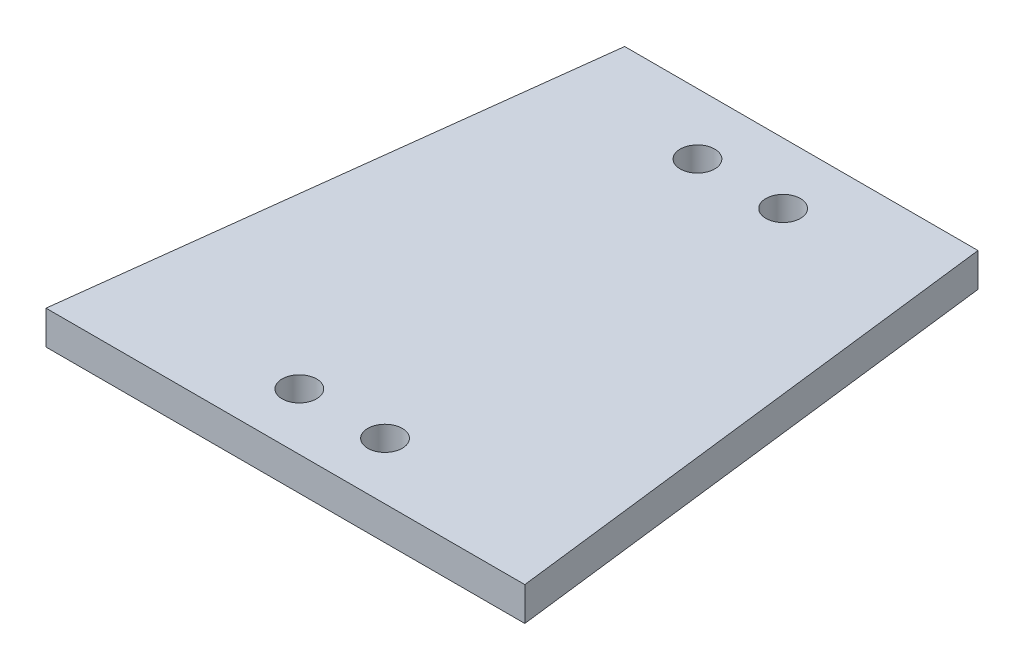
SolidWorks part; units mm, degrees
material "PET"
ref_plane "Front Plane" through (0, 0, 0) normal (0, 0, 1) x (1, 0, 0)
ref_plane "Top Plane" through (0, 0, 0) normal (0, 1, 0) x (1, 0, 0)
ref_plane "Right Plane" through (0, 0, 0) normal (1, 0, 0) x (0, 0, -1)
ref_plane "Plane1" through (0, -14, 0) normal (0, 1, 0) x (1, 0, 0)
sketch "Sketch1" plane through (0, -14, 0) normal (0, 1, 0) x (1, 0, 0)
  line L0 (-28.4185, 23.7577) -> (28.4185, 23.7577)
  line L1 (28.4185, 23.7577) -> (20.9705, 85)
  line L2 (20.9705, 85) -> (-20.9705, 85)
  line L3 (-20.9705, 85) -> (-28.4185, 23.7577)
extrude "Boss-Extrude1" add sketch "Sketch1" against normal blind 4
ref_plane "Plane2" through (0, 0, -64.665) normal (0, 0, -1) x (-1, 0, 0)
sketch "Sketch2" plane through (0, 0, -64.665) normal (0, 0, -1) x (-1, 0, 0)
  line L0 (-3, -29) -> (0, -29)
  line L1 (0, -29) -> (0, -18)
  line L2 (0, -18) -> (-5, -18)
  line L3 (-5, -18) -> (-5, -24)
  line L4 (-5, -24) -> (-3, -24)
  line L5 (-3, -24) -> (-3, -29)
  line L6 (0, -29) -> (0, -18) construction
revolve "Revolve1" add sketch "Sketch2" angle 360 about L6 reverse direction yes
hole_wizard "Ø4.1 (4.1) Diameter Hole1" positions "Sketch4" profile "Sketch3" hole size "Ø4.1" standard "ANSI Metric"
sketch "Sketch4" plane through (0, -14, 0) normal (0, 1, 0) x (1, 0, 0)
  point P0 (-5.085, 30.495)
  point P1 (5.085, 30.495)
  point P2 (5.085, 77.755)
  point P3 (-5.085, 77.755)
sketch "Sketch3" plane through (-5.085, -14, -30.495) normal (1, 0, 0) x (0, 0, 1)
  line L0 (0, 0) -> (0, 15)
  line L1 (0, 15) -> (2.05, 15)
  line L2 (2.05, 15) -> (2.05, 0)
  line L5 (2.05, 0) -> (0, 0)
  line L11 (0, -6.35) -> (0, 107.95) construction
  dimension "Thru Hole Dia." = 4.1
  dimension "Thru Hole Depth" = 15
sketch "Sketch5" plane through (0, -29, 0) normal (0, -1, 0) x (1, 0, 0)
  point P0 (0, -64.665)
